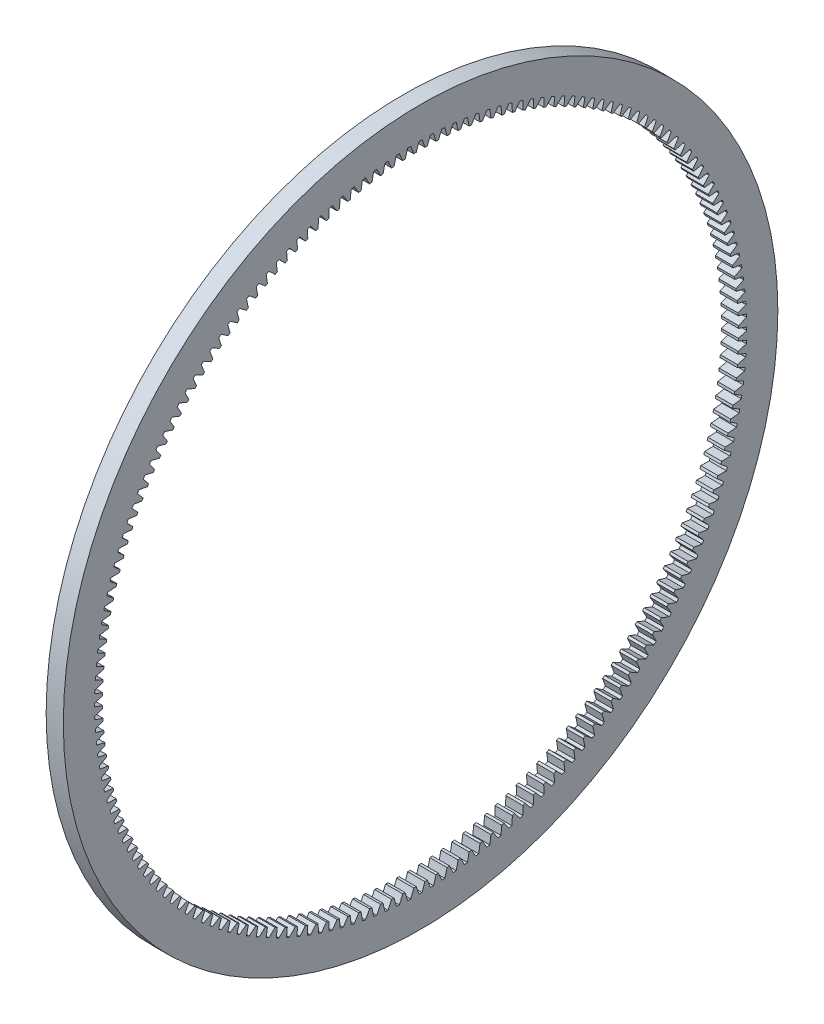
SolidWorks part; units mm, degrees
ref_plane "Plane1" through (0, 0, 0) normal (0, 0, 1) x (1, 0, 0)
ref_plane "Plane2" through (0, 0, 0) normal (0, 1, 0) x (1, 0, 0)
ref_plane "Plane3" through (0, 0, 0) normal (1, 0, 0) x (0, 0, -1)
sketch "HoldingSke" plane through (0, 0, 0) normal (0, 1, 0) x (1, 0, 0)
  line L0 (0, 0) -> (-0.4, 0)
  line L1 (-15, 0) -> (100, 0) construction
  line L2 (0, 0) -> (-2.1039, 2.3779)
  line L3 (0, 0) -> (-11.863, 4.5341)
  line L4 (0, 0) -> (-8.636, 0)
  line L5 (0, 0) -> (-23.7986, -8.8762)
  line L6 (0, 0) -> (-10.5278, -7.1032)
  line L7 (-2.1039, 2.3779) -> (3.3635, 27.1825)
  line L8 (-76.2, 4.8779) -> (-54.61, 4.8779)
  line L9 (-71.009, 38.7566) -> (-53.1078, 45.2721)
  line L10 (-76.2, 71.12) -> (104.1128, 71.12)
  line L11 (0, 0) -> (-12, 0)
  line L12 (-76.2, 101.6) -> (-76.113, 101.6)
  line L13 (24.9733, 27.94) -> (52.9518, 28.4284)
  line L14 (24.9733, 27.94) -> (24.9743, 27.94)
  line L15 (24.9733, 27.94) -> (100.4006, 29.5858)
  circle A0 centre (0, 0) radius 250
  circle A1 centre (0, 0) radius 12.7
  circle A2 centre (0, 0) radius 12.7
  dimension "Num_teeth" = 180
  dimension "Pitch_radius" = 180.3128
  dimension "Width" = 12
  dimension "Diameter" = 500
sketch "BasProSke" plane through (0, 0, 0) normal (0, 1, 0) x (1, 0, 0)
  line L0 (-10, 0) -> (60, 0) construction
  line L1 (0, 222.5) -> (0, 250)
  line L2 (0, 222.5) -> (12, 222.5)
  line L3 (12, 222.5) -> (12, 250)
  line L4 (12, 250) -> (0, 250)
  dimension "Thickness" = 12
  dimension "Diameter" = 500
revolve "Base-Revolve" add sketch "BasProSke" angle 360 about L0
sketch "TooCutSke" plane through (0, 0, 0) normal (1, 0, 0) x (0, 0, -1)
  line L3 (2.181, 224.9894) -> (2.181, 53.6633) construction
  line L4 (0, 0) -> (0, 59.563) construction
  line L5 (0, 0) -> (-1.1925, 68.3171) construction
  line L6 (-104.236, 188.4973) -> (34.5161, 190.9192) construction
  circle A0 centre (0, 0) radius 225 construction
  circle A1 centre (0, 0) radius 228.126 construction
  circle A2 centre (0, 0) radius 190.2878 construction
  circle A3 centre (0, 0) radius 222.4746 construction
  arc A4 (3.0169, 222.4541) -> (1.0541, 228.1236) centre (-104.236, 188.4973) ccw
  arc A5 (3.0169, 222.4541) -> (-3.0169, 222.4541) centre (0, 0) ccw
  arc A6 (1.0541, 228.1236) -> (-1.0541, 228.1236) centre (0, 0) ccw
  arc A7 (-1.0541, 228.1236) -> (-3.0169, 222.4541) centre (104.236, 188.4973) ccw
extrude "ToothCut" cut sketch "TooCutSke" along normal through all
fillet "Breaks" [suppressed] radius 0.25
fillet "RootFillets" [suppressed] radius 0.626
pattern_circular "TeethCuts" count 180 every 2 about axis through (-10, 0, 0) along (1, 0, 0) of "RootFillets", "Breaks", "ToothCut"
equation "' \"Module@HoldingSke\" = 6.35"
equation "' \"Num_teeth@HoldingSke\" = 24"
equation "' \"Ap@HoldingSke\" =  14.5"
equation "' \"Ap@HoldingSke\" = 14.5"
equation "' \"Width@HoldingSke\" = 12"
equation "' \"Diameter@HoldingSke\" = 8 * 25.4"
equation "' \"Show_teeth@HoldingSke\" = 100"
equation "' \"Backlash@HoldingSke\" = 0.009 * 25.4"
equation "' \"Addendum_fac@HoldingSke\" = 1.0"
equation "' \"Dedendum_fac@HoldingSke\" = 1.25"
equation "' \"Dedendum_add@HoldingSke\" = 0.00005 * 25.4"
equation "' \"Clearance_fac@HoldingSke\" = 0.25"
equation "\"Pitch@HoldingSke\" = 1 / \"Module@HoldingSke\" "
equation "\"Overcut_dia@TooCutSke\" = (\"Num_teeth@HoldingSke\" - 2 * \"Addendum_fac@HoldingSke\") / \"Pitch@HoldingSke\" - 0.002 * 25.4"
equation "\"Pitch_dia@TooCutSke\" = \"Num_teeth@HoldingSke\" / \"Pitch@HoldingSke\""
equation "\"Base_dia@TooCutSke\" = \"Num_teeth@HoldingSke\" / \"Pitch@HoldingSke\" * cos((\"Ap@HoldingSke\"  * 3.14159265 / 180)) * 0.90"
equation "\"Root_dia@TooCutSke\" = \"Num_teeth@HoldingSke\"  / \"Pitch@HoldingSke\" + 2 *  \"Dedendum_fac@HoldingSke\"/ \"Pitch@HoldingSke\" + \"Dedendum_add@HoldingSke\" * 2"
equation "\"Half_ang@TooCutSke\" = 180 / \"Num_teeth@HoldingSke\""
equation "\"Half_CT@TooCutSke\" = \"Num_teeth@HoldingSke\" / \"Pitch@HoldingSke\" * sin((3.14159265 / 2 / \"Num_teeth@HoldingSke\")) / 2 + 10 * \"Backlash@HoldingSke\" / 4"
equation "\"Flank_rad@TooCutSke\" = \"Num_teeth@HoldingSke\" / \"Pitch@HoldingSke\" / 4"
equation "\"Radius@RootFillets\"= \"Clearance_fac@HoldingSke\" / \"Pitch@HoldingSke\" + \"Dedendum_add@HoldingSke\""
equation "\"Break_rad@Breaks\" = 0.02 / \"Pitch@HoldingSke\" * 5"
equation "\"Num_teeth@TeethCuts\" = int( \"Show_teeth@HoldingSke\" ) + 1"
equation "\"Num_teeth@TeethCuts\" = ((sgn( \"Num_teeth@TeethCuts\" - \"Num_teeth@HoldingSke\" )-1)*( \"Num_teeth@TeethCuts\" - \"Num_teeth@HoldingSke\" ))/-2+ \"Num_teeth@HoldingSke\""
equation "\"Num_teeth@TeethCuts\" = ((sgn( \"Num_teeth@TeethCuts\" - 2.0)+1)*( \"Num_teeth@TeethCuts\" - 2.0))/2 +2.0"
equation "\"Angle@TeethCuts\" = 360.0 / \"Num_teeth@HoldingSke\""
equation "\"Diameter@BasProSke\" = \"Num_teeth@HoldingSke\"  / \"Pitch@HoldingSke\" + 2 *  \"Dedendum_fac@HoldingSke\"/ \"Pitch@HoldingSke\" + \"Dedendum_add@HoldingSke\" * 2 + 0.002 * 25.4"
equation "\"Diameter@BasProSke\" = ((sgn( \"Diameter@BasProSke\"  - \"Diameter@HoldingSke\" )+1)*( \"Diameter@BasProSke\"  - \"Diameter@HoldingSke\" ))/2 + \"Diameter@HoldingSke\""
equation "\"Inside_diameter@BasProSke\" =  (\"Num_teeth@HoldingSke\" - 2 * \"Addendum_fac@HoldingSke\") / \"Pitch@HoldingSke\" "
equation "\"Thickness@BasProSke\"  = \"Width@HoldingSke\""
